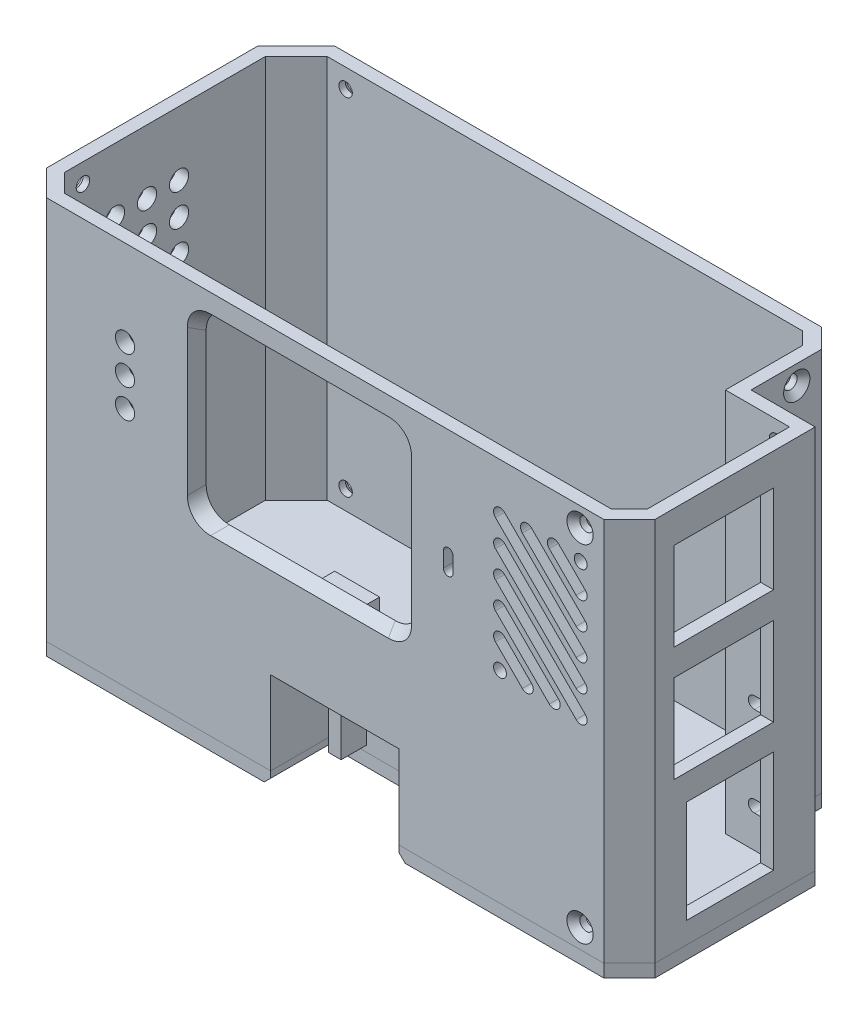
SolidWorks part; units mm, degrees
ref_plane "前视基准面" through (0, 0, 0) normal (0, 0, 1) x (1, 0, 0)
ref_plane "上视基准面" through (0, 0, 0) normal (0, 1, 0) x (1, 0, 0)
ref_plane "右视基准面" through (0, 0, 0) normal (1, 0, 0) x (0, 0, -1)
other "Configuration Table"
sketch "草图1" plane through (0, 0, 0) normal (0, 0, 1) x (1, 0, 0)
  line L1 (-105.5174, 35.9027) -> (-10.5174, 35.9027)
  line L2 (-105.5174, 35.9027) -> (-105.5174, -26.0973)
  line L3 (-105.5174, -26.0973) -> (-10.5174, -26.0973)
  line L4 (-10.5174, 35.9027) -> (-10.5174, -26.0973)
  dimension "D1" = 62
  dimension "D2" = 95
extrude "凸台-拉伸1" add sketch "草图1" along normal blind 43
sketch "草图4" plane through (0, -26.0973, 0) normal (0, -1, 0) x (1, 0, 0)
  line L0 (-10.5174, 43) -> (-10.5174, 0) construction
  line L1 (-10.5174, 14) -> (-20.5174, 14)
  line L2 (-10.5174, 14) -> (-10.5174, 0)
  line L3 (-10.5174, 0) -> (-20.5174, 0)
  line L4 (-20.5174, 14) -> (-20.5174, 0)
  line L5 (-105.5174, 0) -> (-10.5174, 0) construction
  dimension "D1" = 14
  dimension "D2" = 10
extrude "切除-拉伸3" cut sketch "草图4" against normal up to next
chamfer "倒角2" distance 6 angle 45 1 edges at (-105.5174, 4.9027, 0)
chamfer "倒角3" distance 4 angle 45 2 edges at (-105.5174, 4.9027, 43) (-10.5174, 4.9027, 43)
sketch "草图7" plane through (0, 0, 43) normal (0, 0, 1) x (1, 0, 0)
  line L0 (-101.5174, -26.0973) -> (-14.5174, -26.0973) construction
  line L1 (-46.5174, -26.0973) -> (-66.5174, -26.0973)
  line L2 (-46.5174, -26.0973) -> (-46.5174, -6.0973)
  line L3 (-46.5174, -6.0973) -> (-66.5174, -6.0973)
  line L4 (-66.5174, -26.0973) -> (-66.5174, -6.0973)
  line L6 (-10.5174, -26.0973) -> (-10.5174, 35.9027) construction
  dimension "D1" = 36
  dimension "D2" = 20
  dimension "D3" = 20
extrude "切除-拉伸5" cut sketch "草图7" against normal blind 10
shell "抽壳3" thickness 2 removed face at (-54.2952, 35.9027, 22)
sketch "草图9" plane through (0, -6.0973, 0) normal (0, -1, 0) x (1, 0, 0)
  line L0 (-44.5174, 41) -> (-68.5174, 41) construction
  line L1 (-46.5174, 41) -> (-66.5174, 41)
  line L2 (-46.5174, 41) -> (-46.5174, 33)
  line L3 (-46.5174, 33) -> (-66.5174, 33)
  line L4 (-66.5174, 41) -> (-66.5174, 33)
  line L5 (-66.5174, 33) -> (-46.5174, 33) construction
  line L8 (-66.5174, 33) -> (-66.5174, 43) construction
  line L9 (-46.5174, 33) -> (-46.5174, 43) construction
extrude "切除-拉伸6" cut sketch "草图9" against normal blind 10
sketch "草图10" plane through (0, -6.0973, 0) normal (0, -1, 0) x (1, 0, 0)
  line L4 (-66.5174, 43) -> (-66.5174, 41)
  line L5 (-66.5174, 41) -> (-46.5174, 41)
  line L6 (-46.5174, 41) -> (-46.5174, 43)
  line L7 (-46.5174, 43) -> (-66.5174, 43)
  line L8 (-66.5174, 43) -> (-66.5174, 41)
  line L9 (-66.5174, 41) -> (-46.5174, 41)
  line L10 (-46.5174, 41) -> (-46.5174, 43)
  line L11 (-46.5174, 43) -> (-66.5174, 43)
  dimension "D1" = 0
extrude "凸台-拉伸2" add sketch "草图10" along normal blind 5
sketch "草图11" plane through (0, 0, 43) normal (0, 0, 1) x (1, 0, 0)
  line L0 (-97.0174, 3.0227) -> (-76.0174, 3.0227) construction
  line L1 (-44.5121, 32.986) -> (-79.5174, 32.986)
  line L2 (-44.5121, 32.986) -> (-44.5121, 3.0227)
  line L3 (-44.5121, 3.0227) -> (-79.5174, 3.0227)
  line L4 (-79.5174, 32.986) -> (-79.5174, 3.0227)
  arc A0 (-44.0174, 32.8768) -> (-45.0174, 33.0227) centre (-45.0174, 29.5227) ccw construction
extrude "切除-拉伸7" cut sketch "草图11" against normal up to next (2 mm away) draft 25
fillet "圆角1" radius 4 4 edges at (-79.0511, 32.5197, 42) (-79.0511, 3.489, 42) (-44.9784, 3.489, 42) (-44.9784, 32.5197, 42)
sketch "草图12" plane through (0, 0, 33) normal (0, 0, 1) x (1, 0, 0)
  line L0 (-46.5174, -4.0973) -> (-66.5174, -4.0973) construction
  line L1 (-63.5174, -4.0973) -> (-49.5174, -4.0973)
  line L2 (-63.5174, -4.0973) -> (-63.5174, -23.0973)
  line L3 (-63.5174, -23.0973) -> (-49.5174, -23.0973)
  line L4 (-49.5174, -4.0973) -> (-49.5174, -23.0973)
  line L5 (-66.5174, -4.0973) -> (-66.5174, -11.0973) construction
  line L6 (-46.5174, -4.0973) -> (-46.5174, -11.0973) construction
  line L7 (-66.5174, -26.0973) -> (-46.5174, -26.0973) construction
  dimension "D1" = 3
  dimension "D2" = 3
  dimension "D3" = 3
extrude "凸台-拉伸3" add sketch "草图12" along normal blind 4
sketch "草图13" plane through (0, -4.0973, 0) normal (0, 1, 0) x (1, 0, 0)
  line L0 (-44.5174, -31) -> (-68.5174, -31) construction
  line L1 (-61.5174, -31) -> (-51.5174, -31)
  line L2 (-61.5174, -31) -> (-61.5174, -35.5752)
  line L3 (-61.5174, -35.5752) -> (-51.5174, -35.5752)
  line L4 (-51.5174, -31) -> (-51.5174, -35.5752)
  line L5 (-68.5174, -31) -> (-68.5174, -41) construction
  line L6 (-44.5174, -31) -> (-44.5174, -41) construction
  dimension "D1" = 7
  dimension "D2" = 7
extrude "切除-拉伸8" cut sketch "草图13" against normal blind 17
sketch "草图14" plane through (0, 0, 37) normal (0, 0, 1) x (1, 0, 0)
  line L0 (-63.5174, -23.0973) -> (-49.5174, -23.0973) construction
  line L1 (-61.5174, -4.0973) -> (-51.5174, -4.0973)
  line L2 (-61.5174, -4.0973) -> (-61.5174, -23.0973)
  line L3 (-61.5174, -23.0973) -> (-51.5174, -23.0973)
  line L4 (-51.5174, -4.0973) -> (-51.5174, -23.0973)
extrude "切除-拉伸9" cut sketch "草图14" against normal up to surface (4 mm away) up to face at (-56.5174, -14.3473, 33)
chamfer "倒角4" distance 1 angle 45 2 edges at (-66.5174, -26.0973, 38) (-46.5174, -26.0973, 38)
sketch "草图15" plane through (-10.5174, 0, 0) normal (1, 0, 0) x (0, 0, -1)
  line L1 (-34.05, -4.7773) -> (-20.5, -4.7773)
  line L2 (-34.05, -4.7773) -> (-34.05, -20.7773)
  line L3 (-34.05, -20.7773) -> (-20.5, -20.7773)
  line L4 (-20.5, -4.7773) -> (-20.5, -20.7773)
  line L5 (-36, 13.0027) -> (-20.5, 13.0027)
  line L6 (-36, 13.0027) -> (-36, -0.7573)
  line L7 (-36, -0.7573) -> (-20.5, -0.7573)
  line L8 (-20.5, 13.0027) -> (-20.5, -0.7573)
  line L9 (-36, 30.9027) -> (-20.5, 30.9027)
  line L10 (-36, 30.9027) -> (-36, 17.1427)
  line L11 (-36, 17.1427) -> (-20.5, 17.1427)
  line L12 (-20.5, 30.9027) -> (-20.5, 17.1427)
extrude "切除-拉伸10" cut sketch "草图15" against normal blind 2
sketch "草图16" plane through (0, 0, 43) normal (0, 0, 1) x (1, 0, 0)
  line L0 (-38.7974, 19.2043) -> (-38.7974, 16.8043) construction
  line L1 (-38.0444, 19.2043) -> (-38.0444, 16.8043)
  line L2 (-39.5504, 19.2043) -> (-39.5504, 16.8043)
  line L3 (-45.4447, 28.4282) -> (-45.4447, 7.5805) construction
  line L5 (-44.5121, 18.0043) -> (-51.3378, 18.0043) construction
  line L6 (-10.5174, -26.0973) -> (-10.5174, 35.9027) construction
  arc A0 (-38.0444, 19.2043) -> (-39.5504, 19.2043) centre (-38.7974, 19.2043) ccw
  arc A1 (-39.5504, 16.8043) -> (-38.0444, 16.8043) centre (-38.7974, 16.8043) ccw
  point P2 (-38.7974, 18.0043)
  point P14 (-45.4447, 18.0043)
  dimension "D1" = 2.4
  dimension "D2" = 28.28
extrude "切除-拉伸11" cut sketch "草图16" against normal blind 2
sketch "草图17" plane through (0, -26.0973, 0) normal (0, -1, 0) x (1, 0, 0)
  line L0 (-105.5174, 39) -> (-105.5174, 6) construction
  line L1 (-93.9174, 13.067) -> (-84.4174, 13.067)
  line L2 (-93.9174, 13.067) -> (-93.9174, 16.567)
  line L3 (-93.9174, 16.567) -> (-84.4174, 16.567)
  line L4 (-84.4174, 13.067) -> (-84.4174, 16.567)
  line L6 (-93.9174, 20.3114) -> (-84.4174, 20.3114)
  line L7 (-93.9174, 20.3114) -> (-93.9174, 23.8114)
  line L8 (-93.9174, 23.8114) -> (-84.4174, 23.8114)
  line L9 (-84.4174, 20.3114) -> (-84.4174, 23.8114)
  line L10 (-78.1448, 23.5342) -> (-71.5448, 23.5342)
  line L11 (-78.1448, 23.5342) -> (-78.1448, 20.3114)
  line L12 (-78.1448, 20.3114) -> (-71.5448, 20.3114)
  line L13 (-71.5448, 23.5342) -> (-71.5448, 20.3114)
  line L14 (-64.6448, 23.6466) -> (-58.0448, 23.6466)
  line L15 (-64.6448, 23.6466) -> (-64.6448, 20.3114)
  line L16 (-64.6448, 20.3114) -> (-58.0448, 20.3114)
  line L17 (-58.0448, 23.6466) -> (-58.0448, 20.3114)
  line L19 (-83.4263, 17.1002) -> (-76.4263, 17.1002)
  line L20 (-83.4263, 17.1002) -> (-83.4263, 13.067)
  line L21 (-83.4263, 13.067) -> (-76.4263, 13.067)
  line L22 (-76.4263, 17.1002) -> (-76.4263, 13.067)
  line L23 (-74.9763, 17.1002) -> (-67.9763, 17.1002)
  line L24 (-74.9763, 17.1002) -> (-74.9763, 13.067)
  line L25 (-74.9763, 13.067) -> (-67.9763, 13.067)
  line L26 (-67.9763, 17.1002) -> (-67.9763, 13.067)
  line L27 (-51.5174, 16.567) -> (-43.9374, 16.567)
  line L28 (-51.5174, 16.567) -> (-51.5174, 13.767)
  line L29 (-51.5174, 13.767) -> (-43.9374, 13.767)
  line L30 (-43.9374, 16.567) -> (-43.9374, 13.767)
  line L31 (-63.5659, 16.567) -> (-52.9233, 16.567)
  line L32 (-63.5659, 16.567) -> (-63.5659, 14.767)
  line L33 (-63.5659, 14.767) -> (-52.9233, 14.767)
  line L34 (-52.9233, 16.567) -> (-52.9233, 14.767)
  dimension "D1" = 11.6
  dimension "D2" = 27.3726
  dimension "D3" = 6.9
  dimension "D4" = 6.6
  dimension "D5" = 7
  dimension "D6" = 1.45
  dimension "D7" = 9.5
  dimension "D8" = 3.5
  dimension "D9" = 2.8
  dimension "D10" = 54
  dimension "D11" = 7.58
  dimension "D12" = 1.4059
  dimension "D13" = 1.8
extrude "切除-拉伸12" cut sketch "草图17" against normal blind 2
chamfer "倒角9" distance 1 angle 45 12 edges at (-78.1448, -24.0973, 21.9228) (-74.8448, -24.0973, 23.5342) (-71.5448, -24.0973, 21.9228) (-74.8448, -24.0973, 20.3114) (-61.3448, -24.0973, 23.6466) (-64.6448, -24.0973, 21.979) (-58.0448, -24.0973, 21.979) (-61.3448, -24.0973, 20.3114) (-51.5174, -24.0973, 15.167) (-47.7274, -24.0973, 16.567) (-43.9374, -24.0973, 15.167) (-47.7274, -24.0973, 13.767)
fillet "圆角2" radius 1.2 8 edges at (-93.9174, -25.0973, 16.567) (-84.4174, -25.0973, 16.567) (-84.4174, -25.0973, 13.067) (-93.9174, -25.0973, 13.067) (-93.9174, -25.0973, 20.3114) (-93.9174, -25.0973, 23.8114) (-84.4174, -25.0973, 23.8114) (-84.4174, -25.0973, 20.3114)
fillet "圆角3" radius 0.5 18 edges at (-43.9374, -25.5973, 13.767) (-51.5174, -25.5973, 13.767) (-64.6448, -25.5973, 23.6466) (-58.0448, -25.5973, 23.6466) (-71.5448, -25.5973, 23.5342) (-78.1448, -25.5973, 23.5342) (-67.9763, -25.0973, 17.1002) (-74.9763, -25.0973, 17.1002) (-76.4263, -25.0973, 17.1002) (-83.4263, -25.0973, 17.1002) (-83.4263, -25.0973, 13.067) (-74.9763, -25.0973, 13.067) (-76.4263, -25.0973, 13.067) (-67.9763, -25.0973, 13.067) (-63.5659, -25.0973, 14.767) (-63.5659, -25.0973, 16.567) (-52.9233, -25.0973, 16.567) (-52.9233, -25.0973, 14.767)
chamfer "倒角7" distance 1 angle 45 6 edges at (-51.5174, -25.5973, 16.567) (-43.9374, -25.5973, 16.567) (-58.0448, -25.5973, 20.3114) (-64.6448, -25.5973, 20.3114) (-78.1448, -25.5973, 20.3114) (-71.5448, -25.5973, 20.3114)
sketch "草图18" plane through (0, 0, 43) normal (0, 0, 1) x (1, 0, 0)
  line L1 (-79.5174, 18.0043) -> (-81.9758, 18.0043) construction
  circle A0 centre (-89.2561, 13.5043) radius 1.5
  circle A1 centre (-89.2561, 18.0043) radius 1.5
  circle A2 centre (-89.2561, 22.5043) radius 1.5
  dimension "D3" = 3
  dimension "D2" = 3
extrude "切除-拉伸13" cut sketch "草图18" against normal blind 2
sketch "草图20" plane through (0, -24.0973, 0) normal (0, 1, 0) x (1, 0, 0)
  line L1 (-83.4263, -13.567) -> (-76.9263, -13.567)
  line L2 (-83.4263, -13.567) -> (-83.4263, -16.6002)
  line L3 (-83.4263, -16.6002) -> (-76.9263, -16.6002)
  line L4 (-76.9263, -13.567) -> (-76.9263, -16.6002)
  line L5 (-74.9763, -13.567) -> (-68.4763, -13.567)
  line L6 (-74.9763, -13.567) -> (-74.9763, -16.6002)
  line L7 (-74.9763, -16.6002) -> (-68.4763, -16.6002)
  line L8 (-68.4763, -13.567) -> (-68.4763, -16.6002)
extrude "凸台-拉伸4" add sketch "草图20" against normal blind 1
sketch "草图21" plane through (0, -25.0973, 0) normal (0, -1, 0) x (1, 0, 0)
  line L0 (-76.9263, 13.567) -> (-83.4263, 13.567) construction
  line L1 (-76.9263, 16.6002) -> (-80.9263, 16.6002)
  line L2 (-76.9263, 16.6002) -> (-76.9263, 13.567)
  line L3 (-76.9263, 13.567) -> (-80.9263, 13.567)
  line L4 (-80.9263, 16.6002) -> (-80.9263, 13.567)
  line L5 (-68.4763, 13.567) -> (-74.9763, 13.567) construction
  line L6 (-68.4763, 16.6002) -> (-72.4763, 16.6002)
  line L7 (-68.4763, 16.6002) -> (-68.4763, 13.567)
  line L8 (-68.4763, 13.567) -> (-72.4763, 13.567)
  line L9 (-72.4763, 16.6002) -> (-72.4763, 13.567)
  dimension "D1" = 4
extrude "凸台-拉伸5" add sketch "草图21" along normal up to surface (1 mm away) up to face at (-61.3448, -26.0973, 22.1299)
fillet "圆角4" radius 0.5 10 edges at (-74.9763, -25.0973, 15.0836) (-83.4263, -25.0973, 15.0836) (-80.9263, -25.5973, 13.567) (-80.9263, -25.5973, 16.6002) (-72.4763, -25.5973, 16.6002) (-72.4763, -25.5973, 13.567) (-68.4763, -25.0973, 16.6002) (-68.4763, -25.0973, 13.567) (-76.9263, -25.0973, 13.567) (-76.9263, -25.0973, 16.6002)
chamfer "倒角10" distance 2 angle 45 1 edges at (-22.5174, 5.9027, 2)
chamfer "倒角11" distance 3 angle 45 1 edges at (-20.5174, 4.9027, 0)
sketch "草图26" plane through (-20.5174, 0, 0) normal (1, 0, 0) x (0, 0, -1)
  line L0 (-10, 18.9027) -> (-10, -21.0973) construction
  line L1 (-8.6566, 18.9027) -> (-8.6566, -21.0973)
  line L2 (-11.3434, 18.9027) -> (-11.3434, -21.0973)
  line L3 (-14, -26.0973) -> (-3, -26.0973) construction
  line L5 (0, 35.9027) -> (0, -26.0973) construction
  arc A0 (-8.6566, 18.9027) -> (-11.3434, 18.9027) centre (-10, 18.9027) ccw
  arc A1 (-11.3434, -21.0973) -> (-8.6566, -21.0973) centre (-10, -21.0973) ccw
  point P2 (-10, -1.0973)
  dimension "D1" = 40
  dimension "D2" = 25
  dimension "D3" = 10
extrude "切除-拉伸15" cut sketch "草图26" against normal up to next
sketch "草图27" plane through (0, 0, 43) normal (0, 0, 1) x (1, 0, 0)
  line L0 (-10.5174, 35.9027) -> (-10.5174, -26.0973) construction
  line L1 (-101.5174, 37.9027) -> (-14.5174, 37.9027) construction
  line L2 (-22.3174, 28.4027) -> (-18.1174, 24.2027) construction
  line L3 (-21.6103, 29.1098) -> (-17.4103, 24.9098)
  line L4 (-23.0245, 27.6956) -> (-18.8245, 23.4956)
  line L5 (-26.5174, 28.4027) -> (-18.1174, 20.0027) construction
  line L6 (-25.8103, 29.1098) -> (-17.4103, 20.7098)
  line L7 (-27.2245, 27.6956) -> (-18.8245, 19.2956)
  line L8 (-30.7174, 28.4027) -> (-18.1174, 15.8027) construction
  line L9 (-30.0103, 29.1098) -> (-17.4103, 16.5098)
  line L10 (-31.4245, 27.6956) -> (-18.8245, 15.0956)
  line L11 (-30.7174, 24.2027) -> (-18.1174, 11.6027) construction
  line L12 (-30.0103, 24.9098) -> (-17.4103, 12.3098)
  line L13 (-31.4245, 23.4956) -> (-18.8245, 10.8956)
  line L14 (-30.7174, 20.0027) -> (-18.1174, 7.4027) construction
  line L15 (-30.0103, 20.7098) -> (-17.4103, 8.1098)
  line L16 (-31.4245, 19.2956) -> (-18.8245, 6.6956)
  line L17 (-22.3174, 7.4027) -> (-30.7174, 15.8027) construction
  line L18 (-23.0245, 6.6956) -> (-31.4245, 15.0956)
  line L19 (-21.6103, 8.1098) -> (-30.0103, 16.5098)
  line L20 (-30.7174, 11.6027) -> (-26.5174, 7.4027) construction
  line L21 (-30.0103, 12.3098) -> (-25.8103, 8.1098)
  line L22 (-31.4245, 10.8956) -> (-27.2245, 6.6956)
  circle A0 centre (-18.1174, 28.4027) radius 1
  circle A1 centre (-22.3174, 28.4027) radius 1 construction
  circle A2 centre (-26.5174, 28.4027) radius 1 construction
  circle A3 centre (-30.7174, 28.4027) radius 1 construction
  circle A6 centre (-30.7174, 24.2027) radius 1 construction
  circle A9 centre (-30.7174, 20.0027) radius 1 construction
  circle A12 centre (-30.7174, 15.8027) radius 1 construction
  circle A15 centre (-30.7174, 11.6027) radius 1 construction
  circle A16 centre (-22.3174, 7.4027) radius 1 construction
  circle A17 centre (-26.5174, 7.4027) radius 1 construction
  circle A18 centre (-30.7174, 7.4027) radius 1
  circle A25 centre (-18.1174, 24.2027) radius 1 construction
  circle A26 centre (-18.1174, 20.0027) radius 1 construction
  circle A27 centre (-18.1174, 15.8027) radius 1 construction
  circle A28 centre (-18.1174, 11.6027) radius 1 construction
  circle A29 centre (-18.1174, 7.4027) radius 1 construction
  circle A31 centre (-22.3174, 24.2027) radius 1 [skipped]
  circle A32 centre (-26.5174, 24.2027) radius 1 [skipped]
  circle A33 centre (-22.3174, 20.0027) radius 1 [skipped]
  circle A34 centre (-26.5174, 20.0027) radius 1 [skipped]
  circle A35 centre (-22.3174, 15.8027) radius 1 [skipped]
  circle A36 centre (-26.5174, 15.8027) radius 1 [skipped]
  circle A37 centre (-22.3174, 11.6027) radius 1 [skipped]
  circle A38 centre (-26.5174, 11.6027) radius 1 [skipped]
  arc A39 (-21.6103, 29.1098) -> (-23.0245, 27.6956) centre (-22.3174, 28.4027) ccw
  arc A40 (-18.8245, 23.4956) -> (-17.4103, 24.9098) centre (-18.1174, 24.2027) ccw
  arc A41 (-25.8103, 29.1098) -> (-27.2245, 27.6956) centre (-26.5174, 28.4027) ccw
  arc A42 (-18.8245, 19.2956) -> (-17.4103, 20.7098) centre (-18.1174, 20.0027) ccw
  arc A43 (-30.0103, 29.1098) -> (-31.4245, 27.6956) centre (-30.7174, 28.4027) ccw
  arc A44 (-18.8245, 15.0956) -> (-17.4103, 16.5098) centre (-18.1174, 15.8027) ccw
  arc A45 (-30.0103, 24.9098) -> (-31.4245, 23.4956) centre (-30.7174, 24.2027) ccw
  arc A46 (-18.8245, 10.8956) -> (-17.4103, 12.3098) centre (-18.1174, 11.6027) ccw
  arc A47 (-30.0103, 20.7098) -> (-31.4245, 19.2956) centre (-30.7174, 20.0027) ccw
  arc A48 (-18.8245, 6.6956) -> (-17.4103, 8.1098) centre (-18.1174, 7.4027) ccw
  arc A49 (-23.0245, 6.6956) -> (-21.6103, 8.1098) centre (-22.3174, 7.4027) ccw
  arc A50 (-30.0103, 16.5098) -> (-31.4245, 15.0956) centre (-30.7174, 15.8027) ccw
  arc A51 (-30.0103, 12.3098) -> (-31.4245, 10.8956) centre (-30.7174, 11.6027) ccw
  arc A52 (-27.2245, 6.6956) -> (-25.8103, 8.1098) centre (-26.5174, 7.4027) ccw
  point P4 (-20.2174, 26.3027)
  point P17 (-22.3174, 24.2027)
  point P24 (-24.4174, 22.1027)
  point P33 (-24.4174, 17.9027)
  point P46 (-24.4174, 13.7027)
  point P51 (-26.5174, 11.6027)
  point P56 (-28.6174, 9.5027)
  dimension "D3" = 2
  dimension "D1" = 7.6
  dimension "D2" = 9.5
  dimension "D4" = 4
  dimension "D5" = 6
sketch "草图28" plane through (-105.5174, 0, 0) normal (-1, 0, 0) x (0, 0, 1)
  line L0 (39, 37.9027) -> (43, 37.9027) construction
  line L1 (43, 37.9027) -> (43, 35.9027) construction
  circle A0 centre (35.3, 25.9027) radius 1.5
  circle A1 centre (30.3, 25.9027) radius 1.5
  circle A2 centre (25.3, 25.9027) radius 1.5
  circle A3 centre (20.3, 25.9027) radius 1.5
  circle A4 centre (30.3, 20.9027) radius 1.5
  circle A5 centre (25.3, 20.9027) radius 1.5
  circle A6 centre (20.3, 20.9027) radius 1.5
  circle A7 centre (30.3, 15.9027) radius 1.5
  circle A8 centre (25.3, 15.9027) radius 1.5
  circle A9 centre (20.3, 15.9027) radius 1.5
  circle A10 centre (30.3, 10.9027) radius 1.5
  circle A11 centre (25.3, 10.9027) radius 1.5
  circle A12 centre (20.3, 10.9027) radius 1.5
  circle A13 centre (30.3, 5.9027) radius 1.5
  circle A14 centre (25.3, 5.9027) radius 1.5
  circle A15 centre (20.3, 5.9027) radius 1.5
  circle A16 centre (30.3, 0.9027) radius 1.5
  circle A17 centre (25.3, 0.9027) radius 1.5
  circle A18 centre (20.3, 0.9027) radius 1.5
  circle A19 centre (30.3, -4.0973) radius 1.5
  circle A20 centre (25.3, -4.0973) radius 1.5
  circle A21 centre (20.3, -4.0973) radius 1.5
  circle A22 centre (30.3, -9.0973) radius 1.5
  circle A23 centre (25.3, -9.0973) radius 1.5
  circle A24 centre (20.3, -9.0973) radius 1.5
  circle A25 centre (35.3, 20.9027) radius 1.5
  circle A26 centre (35.3, 15.9027) radius 1.5
  circle A27 centre (35.3, 10.9027) radius 1.5
  circle A28 centre (35.3, 5.9027) radius 1.5
  circle A29 centre (35.3, 0.9027) radius 1.5
  circle A30 centre (35.3, -4.0973) radius 1.5
  circle A31 centre (35.3, -9.0973) radius 1.5
  circle A32 centre (35.3, -14.0973) radius 1.5
  circle A33 centre (30.3, -14.0973) radius 1.5
  circle A34 centre (25.3, -14.0973) radius 1.5
  circle A35 centre (20.3, -14.0973) radius 1.5
  dimension "D3" = 3
  dimension "D1" = 12
  dimension "D2" = 7.7
  dimension "D4" = 4
  dimension "D5" = 9
extrude "切除-拉伸17" cut sketch "草图28" against normal up to next (2 mm away)
sketch "草图29" plane through (-105.5174, 0, 0) normal (-1, 0, 0) x (0, 0, 1)
  line L0 (39, -26.0973) -> (6, -26.0973) construction
  circle A0 centre (35.3017, 32.9027) radius 1.05
  circle A1 centre (35.3017, -21.0973) radius 1.2021
  point P5 (0, 0)
  dimension "D1" = 2.1
  dimension "D2" = 5
extrude "切除-拉伸18" cut sketch "草图29" against normal up to next
sketch "草图30" plane through (0, 0, 0) normal (0, 0, -1) x (-1, 0, 0)
  line L0 (99.5174, -26.0973) -> (23.5174, -26.0973) construction
  circle A0 centre (95.8191, 32.9027) radius 1.05
  circle A1 centre (95.8191, -21.0973) radius 1.05
  point P5 (0, 0)
  dimension "D1" = 2.1
  dimension "D2" = 5
extrude "切除-拉伸19" cut sketch "草图30" against normal up to next
sketch "草图31" plane through (-20.5174, 0, 0) normal (1, 0, 0) x (0, 0, -1)
  line L0 (-14, -26.0973) -> (-3, -26.0973) construction
  circle A0 centre (-6.8698, 32.9027) radius 1.05
  circle A1 centre (-6.8698, -21.0973) radius 1.05
  point P5 (0, 0)
  point P6 (0, 0)
  dimension "D1" = 2.1
  dimension "D2" = 5
extrude "切除-拉伸20" cut sketch "草图31" against normal up to next
sketch "草图32" plane through (0, 0, 14) normal (0, 0, -1) x (-1, 0, 0)
  line L0 (10.5174, -26.0973) -> (20.5174, -26.0973) construction
  circle A0 centre (14.6174, 32.9027) radius 1.05
  circle A1 centre (14.6174, -21.0973) radius 1.05
  point P7 (0, 0)
  dimension "D1" = 2.1
  dimension "D2" = 5
extrude "切除-拉伸21" cut sketch "草图32" against normal up to next
sketch "草图33" plane through (0, 0, 43) normal (0, 0, 1) x (1, 0, 0)
  line L1 (-45.5174, -26.0973) -> (-14.5174, -26.0973) construction
  circle A0 centre (-18.2157, 32.9027) radius 1.05
  circle A1 centre (-18.2157, -21.0973) radius 1.05
  point P5 (0, 0)
  dimension "D1" = 2.1
  dimension "D2" = 5
extrude "切除-拉伸22" cut sketch "草图33" against normal up to next
chamfer "倒角20" distance 1 angle 45 10 edges at (-96.8691, 32.9027, 0) (-105.5174, 31.8527, 35.3017) (-17.1657, 32.9027, 43) (-15.6674, 32.9027, 14) (-20.5174, 32.9027, 5.8198) (-17.1657, -21.0973, 43) (-15.6674, -21.0973, 14) (-96.8691, -21.0973, 0) (-105.5174, -22.2995, 35.3017) (-20.5174, -21.0973, 5.8198)
sketch "草图34" plane through (0, 0, 14) normal (0, 0, -1) x (-1, 0, 0)
  line L0 (18.0174, -4.0973) -> (14.0174, -4.0973) construction
  line L1 (18.0174, -5.0973) -> (14.0174, -5.0973)
  line L2 (18.0174, -3.0973) -> (14.0174, -3.0973)
  line L3 (18.0174, -18.0973) -> (14.0174, -18.0973) construction
  line L4 (18.0174, -19.0973) -> (14.0174, -19.0973)
  line L5 (18.0174, -17.0973) -> (14.0174, -17.0973)
  line L7 (20.5174, 35.9027) -> (20.5174, -26.0973) construction
  arc A0 (18.0174, -5.0973) -> (18.0174, -3.0973) centre (18.0174, -4.0973) ccw
  arc A1 (14.0174, -3.0973) -> (14.0174, -5.0973) centre (14.0174, -4.0973) ccw
  arc A2 (18.0174, -19.0973) -> (18.0174, -17.0973) centre (18.0174, -18.0973) ccw
  arc A3 (14.0174, -17.0973) -> (14.0174, -19.0973) centre (14.0174, -18.0973) ccw
  point P3 (16.0174, -4.0973)
  point P8 (16.0174, -18.0973)
  dimension "D1" = 1
  dimension "D2" = 4
  dimension "D3" = 2.5
  dimension "D4" = 14
extrude "切除-拉伸25" cut sketch "草图34" against normal up to next (2 mm away) draft 2
extrude "切除-拉伸26" cut sketch "草图27" against normal up to next
split "分割1" bodies to split 138 resulting bodies 139 140 split by face at (-47.7274, -24.0973, 15.167)
